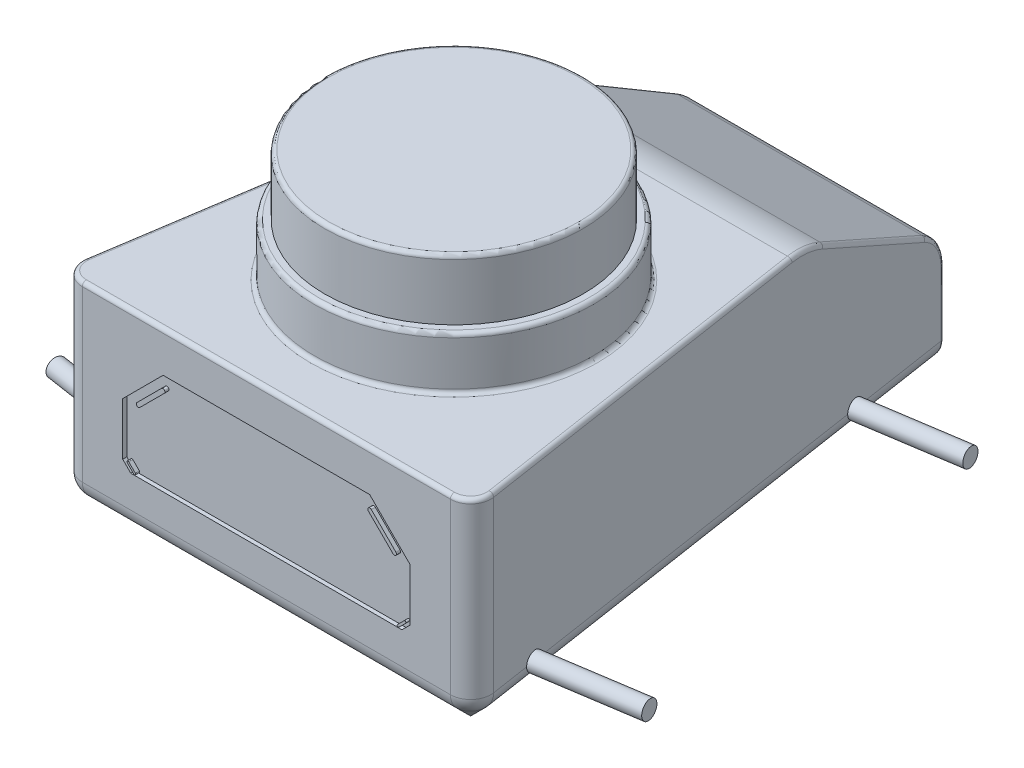
SolidWorks part; units mm, degrees
ref_plane "Front Plane" through (0, 0, 0) normal (0, 0, 1) x (1, 0, 0)
ref_plane "Top Plane" through (0, 0, 0) normal (0, 1, 0) x (1, 0, 0)
ref_plane "Right Plane" through (0, 0, 0) normal (1, 0, 0) x (0, 0, -1)
sketch "Sketch1" plane through (0, 0, 0) normal (0, 1, 0) x (1, 0, 0)
  line L0 (-51.3981, 0) -> (51.3981, 0)
  line L1 (-51.3981, 0) -> (-30.3414, 137.3808)
  line L2 (-30.3414, 137.3808) -> (30.3414, 137.3808)
  line L4 (51.3981, 0) -> (30.3414, 137.3808)
  point P4 (0, 0)
  point P10 (0, 0)
extrude "Boss-Extrude1" add sketch "Sketch1" along normal blind 50
ref_plane "Plane1" through (0, 0, 0) normal (1, 0, 0) x (0, 0, -1)
sketch "Sketch6" plane through (0, 0, 0) normal (1, 0, 0) x (0, 0, -1)
  line L0 (92.4697, 52.8242) -> (139.2927, 28.0643)
  line L1 (139.2927, 28.0643) -> (139.2927, 52.8242)
  line L2 (139.2927, 52.8242) -> (92.4697, 52.8242)
extrude "Cut-Extrude5" cut sketch "Sketch6" against normal mid plane 111
fillet "Fillet2" radius 20 1 edges at (0, 50, -97.8104)
fillet "Fillet3" radius 10 1 edges at (0, 29.0753, -137.3808)
fillet "Fillet4" radius 5 2 edges at (-51.3981, 25, 0) (51.3981, 25, 0)
chamfer "Chamfer2" distance 5 angle 45 5 edges at (-40.4285, 0, -71.5692) (40.4285, 0, -71.5692) (-49.3673, 0, -1.7433) (49.3673, 0, -1.7433) (0, 0, 0)
sketch "Sketch7" plane through (0, 0, 0) normal (0, 0, 1) x (1, 0, 0)
  line L0 (-35.5733, 17) -> (-33.5733, 15)
  line L1 (33.5733, 15) -> (35.5733, 17)
  line L2 (-25.6199, 36.6417) -> (-31.7193, 30.5423) construction
  line L3 (-25.2664, 36.2881) -> (-31.3658, 30.1887)
  line L4 (-25.5733, 40) -> (-35.5733, 30)
  line L5 (35.5733, 30) -> (25.5733, 40)
  line L6 (-25.9735, 36.9953) -> (-32.0729, 30.8958)
  line L7 (-34.2681, 17) -> (-32.649, 15.381) construction
  line L8 (-35.5733, 40) -> (-35.5733, 15)
  line L9 (-35.5733, 15) -> (35.5733, 15)
  line L10 (35.5733, 15) -> (35.5733, 40)
  line L11 (35.5733, 40) -> (-35.5733, 40)
  line L12 (-35.5733, 30) -> (-35.5733, 17)
  line L13 (-33.5733, 15) -> (33.5733, 15)
  line L14 (35.5733, 17) -> (35.5733, 30)
  line L15 (25.5733, 40) -> (-25.5733, 40)
  line L16 (-34.0785, 17.1895) -> (-32.4595, 15.5705)
  line L17 (-34.4576, 16.8105) -> (-32.8386, 15.1914)
  line L18 (0, 15) -> (0, 34.5988) construction
  line L19 (25.6199, 36.6417) -> (31.7193, 30.5423) construction
  line L20 (25.2664, 36.2881) -> (31.3658, 30.1887)
  line L21 (25.9735, 36.9953) -> (32.0729, 30.8958)
  line L22 (34.2681, 17) -> (32.649, 15.381) construction
  line L23 (34.0785, 17.1895) -> (32.4595, 15.5705)
  line L24 (34.4576, 16.8105) -> (32.8386, 15.1914)
  arc A0 (-25.2664, 36.2881) -> (-25.9735, 36.9953) centre (-25.6199, 36.6417) ccw
  arc A1 (-32.0729, 30.8958) -> (-31.3658, 30.1887) centre (-31.7193, 30.5423) ccw
  arc A2 (-34.0785, 17.1895) -> (-34.4576, 16.8105) centre (-34.2681, 17) ccw
  arc A3 (-32.8386, 15.1914) -> (-32.4595, 15.5705) centre (-32.649, 15.381) ccw
  arc A4 (25.2664, 36.2881) -> (25.9735, 36.9953) centre (25.6199, 36.6417) cw
  arc A5 (32.0729, 30.8958) -> (31.3658, 30.1887) centre (31.7193, 30.5423) cw
  arc A6 (34.0785, 17.1895) -> (34.4576, 16.8105) centre (34.2681, 17) cw
  arc A7 (32.8386, 15.1914) -> (32.4595, 15.5705) centre (32.649, 15.381) cw
  point P14 (-28.6696, 33.592)
  point P19 (-33.4585, 16.1905)
  point P32 (28.6696, 33.592)
  point P39 (33.4585, 16.1905)
  dimension "D2" = 1
  dimension "D1" = 10
extrude "Cut-Extrude6" cut sketch "Sketch7" against normal blind 1
fillet "Fillet5" radius 5 5 edges at (-40.4285, 5, -71.5692) (-49.3673, 5, -1.7433) (40.4285, 5, -71.5692) (49.3673, 5, -1.7433) (0, 5, 0)
fillet "Fillet6" radius 1 17 edges at (-27.0714, 1.7678, -137.3808) (-29.9563, 5.1577, -137.3808) (-30.3414, 15.0612, -137.3808) (-30.5612, 28.2114, -135.9467) (-33.4458, 39.7858, -117.1264) (-36.4288, 49.4114, -97.6644) (-43.8413, 50, -49.3028) (-49.3673, 50, -1.7433) (0, 50, 0) (49.3673, 50, -1.7433) (27.0714, 1.7678, -137.3808) (29.9563, 5.1577, -137.3808) (30.3414, 15.0612, -137.3808) (30.5612, 28.2114, -135.9467) (33.4458, 39.7858, -117.1264) (36.4288, 49.4114, -97.6644) (43.8413, 50, -49.3028)
sketch "Sketch8" plane through (0, 50, 0) normal (0, 1, 0) x (1, 0, 0)
  line L0 (0, 0) -> (0, 92.848) construction
  line L1 (36.1553, 92.848) -> (-36.1553, 92.848) construction
  circle A0 centre (0, 46.424) radius 34.5275
extrude "Boss-Extrude2" add sketch "Sketch8" along normal blind 13
fillet "Fillet7" radius 1 1 edges at (0, 63, -11.8965)
fillet "Fillet8" radius 1 1 edges at (0, 50, -80.9515)
sketch "Sketch9" plane through (0, 63, 0) normal (0, 1, 0) x (1, 0, 0)
  circle A0 centre (0, 46.424) radius 32
  dimension "D1" = 64
extrude "Boss-Extrude3" add sketch "Sketch9" along normal blind 15
fillet "Fillet9" radius 1 1 edges at (0, 78, -14.424)
sketch "Sketch10" plane through (50.2183, 0, -7.6971) normal (0.9885, 0, -0.1515) x (-0.1515, 0, -0.9885)
  line L0 (-1.9622, 7.0711) -> (130.3398, 7.0711) construction
  circle A0 centre (105.0378, 7.0711) radius 2.25
  circle A1 centre (10.0378, 7.0711) radius 2.25
  dimension "D4" = 4.5
  dimension "D1" = 95
  dimension "D2" = 12
  dimension "D3" = 25.302
extrude "Boss-Extrude4" add sketch "Sketch10" along normal blind 25
sketch "Sketch11" plane through (-50.2183, 0, -7.6971) normal (-0.9885, 0, -0.1515) x (-0.1515, 0, 0.9885)
  line L0 (-130.3398, 7.0711) -> (1.9622, 7.0711) construction
  circle A0 centre (-105.0378, 7.0711) radius 2.25
  circle A1 centre (-10.0378, 7.0711) radius 2.2546
  dimension "D4" = 4.5
  dimension "D1" = 95
  dimension "D2" = 12
  dimension "D3" = 25.302
extrude "Boss-Extrude5" add sketch "Sketch11" along normal blind 25
scale "Scale1" scale about centroid uniform scaling yes scale factor 1
